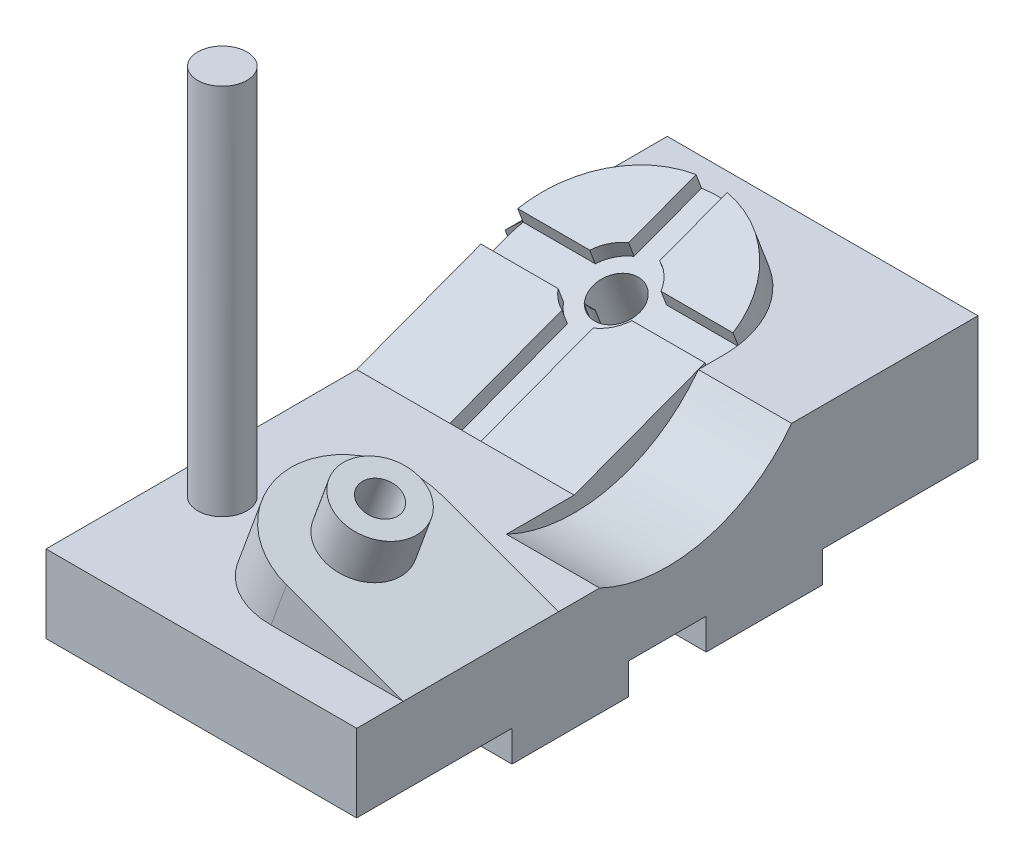
SolidWorks part; units mm, degrees
material "6061 Alloy"
ref_plane "Front Plane" through (0, 0, 0) normal (0, 0, 1) x (1, 0, 0)
ref_plane "Top Plane" through (0, 0, 0) normal (0, 1, 0) x (1, 0, 0)
ref_plane "Right Plane" through (0, 0, 0) normal (1, 0, 0) x (0, 0, -1)
sketch "Sketch1" plane through (0, 0, 0) normal (1, 0, 0) x (0, 0, -1)
  line L0 (173.8899, 19.6785) -> (173.8899, -20.3215)
  line L1 (123.8899, -20.3215) -> (123.8899, -30.3215)
  line L2 (123.8899, -30.3215) -> (86.3899, -30.3215)
  line L3 (86.3899, -30.3215) -> (86.3899, -20.3215)
  line L4 (86.3899, -20.3215) -> (61.3899, -20.3215)
  line L5 (61.3899, -20.3215) -> (61.3899, -30.3215)
  line L6 (61.3899, -30.3215) -> (23.8899, -30.3215)
  line L7 (23.8899, -30.3215) -> (23.8899, -20.3215)
  line L8 (23.8899, -20.3215) -> (-26.1101, -20.3215)
  line L9 (-26.1101, -20.3215) -> (-26.1101, 4.6785)
  line L10 (-26.1101, 4.6785) -> (52.0954, 4.6785)
  line L11 (113.8899, 19.6785) -> (173.8899, 19.6785)
  line L12 (173.8899, -20.3215) -> (123.8899, -20.3215)
  line L13 (73.8899, 4.6785) -> (73.8899, 49.6785) construction
  arc A1 (52.0954, 4.6785) -> (113.8899, 19.6785) centre (73.8899, 49.6785) ccw
  point P4 (-26.1101, -7.8215)
  point P17 (73.8899, 49.6785)
  dimension "D13" = 45
  dimension "D14" = 60
  dimension "D15" = 50
  dimension "D2" = 100
  dimension "D3" = 25
  dimension "D4" = 50
  dimension "D5" = 37.5
  dimension "D6" = 10
  dimension "D7" = 10
  dimension "D8" = 35
  dimension "D9" = 200
  dimension "D10" = 40
  dimension "D11" = 50
  dimension "D12" = 10
extrude "Boss-Extrude1" add sketch "Sketch1" along normal blind 30
sketch "Sketch2" plane through (0, 0, 0) normal (-1, 0, 0) x (0, 0, 1)
  line L0 (26.1101, 4.6785) -> (-73.8899, 4.6785)
  line L1 (-73.8899, 4.6785) -> (-113.8899, 19.6785)
  line L2 (-113.8899, 19.6785) -> (-173.8899, 19.6785)
  line L3 (-173.8899, 19.6785) -> (-173.8899, -20.3215)
  line L4 (-173.8899, -20.3215) -> (-123.8899, -20.3215)
  line L5 (-123.8899, -30.3215) -> (-123.8899, -20.3215) construction
  line L6 (-123.8899, -20.3215) -> (-173.8899, -20.3215) construction
  line L7 (-123.8899, -20.3215) -> (-123.8899, -30.3215)
  line L8 (-123.8899, -30.3215) -> (-86.3899, -30.3215)
  line L9 (-86.3899, -30.3215) -> (-86.3899, -20.3215)
  line L10 (-86.3899, -20.3215) -> (-86.3899, -30.3215) construction
  line L11 (-86.3899, -20.3215) -> (-61.3899, -20.3215)
  line L12 (-61.3899, -20.3215) -> (-61.3899, -30.3215)
  line L13 (-61.3899, -30.3215) -> (-23.8899, -30.3215)
  line L14 (-23.8899, -30.3215) -> (-23.8899, -20.3215)
  line L15 (-23.8899, -20.3215) -> (26.1101, -20.3215)
  line L16 (26.1101, -20.3215) -> (26.1101, 4.6785)
extrude "Boss-Extrude2" add sketch "Sketch2" along normal blind 70
sketch "Sketch3" plane through (0, -20.1909, -7.5716) normal (0, 0.9363, 0.3511) x (1, 0, 0)
  line L0 (-35, 70.828) -> (-35, 108.328) construction
  line L1 (-70, 70.828) -> (0, 70.828) construction
  line L2 (30, 169.7278) -> (30, 113.548) construction
  line L3 (-70, 113.548) -> (-70, 169.7278) construction
  line L4 (0, 70.828) -> (0, 113.548) construction
  line L5 (-70, 120.828) -> (-70, 115.828) construction
  line L6 (-70, 115.828) -> (-46.4564, 115.828)
  line L7 (0, -35.899) -> (0, 35.899) construction
  line L8 (0, 115.828) -> (0, 120.828)
  line L9 (-0.359, 125.828) -> (-23.5436, 125.828)
  line L10 (-70, 120.828) -> (-70, 115.828)
  line L11 (-35, 133.328) -> (-35, 155.828) construction
  line L12 (-70, 115.828) -> (-70, 70.828)
  line L13 (-70, -22.8049) -> (-70, 70.828) construction
  line L14 (-40, 155.469) -> (-40, 132.2845)
  line L15 (-70, 113.548) -> (0, 113.548) construction
  line L16 (-30, 70.828) -> (-30, 109.3716)
  line L17 (-70, 70.828) -> (-70, 113.548) construction
  line L18 (-70, 70.828) -> (0, 70.828)
  line L19 (0, 70.828) -> (0, 115.828)
  line L20 (-40, 109.3716) -> (-40, 70.828)
  line L22 (-30, 132.2845) -> (-30, 155.469)
  line L23 (-23.5436, 115.828) -> (0, 115.828)
  line L25 (-46.4564, 125.828) -> (-69.641, 125.828)
  circle A0 centre (-35, 120.828) radius 7.5
  circle A1 centre (-35, 120.828) radius 12.5
  arc A2 (-70, 120.828) -> (0, 120.828) centre (-35, 120.828) cw
  line M7 (0, 70.828) -> (0, 113.548)
  line M8 (0, 113.548) -> (-70, 113.548)
  line M9 (-70, 113.548) -> (-70, 70.828)
  line M10 (-70, 70.828) -> (0, 70.828)
  dimension "D1" = 15
  dimension "D2" = 25
  dimension "D3" = 0.359
  dimension "D4" = 30
  dimension "D5" = 2.28
  dimension "D6" = 7.28
sketch "Sketch5" plane through (30, 0, 0) normal (1, 0, 0) x (0, 0, -1)
  line L0 (157.8764, 19.6785) -> (201.3703, -5.4327) construction
  line L1 (173.8899, 19.6785) -> (113.8899, 19.6785) construction
  line L2 (157.8764, 19.6785) -> (203.9867, 19.6785) construction
  line L3 (157.8764, 19.6785) -> (187.5187, 36.7924) construction
  dimension "D1" = 30
  dimension "D2" = 150
extrude "Boss-Extrude4" add sketch "Sketch3" against normal blind 25 contours A1 L20 M8 M9 M10 | A1 L16 M10 M7 M8 | A2 L22 A1 L9 | A2 L25 A1 L14 | A2 L14 A1 L22 | A2 L10 L6 A1 L25 | A1 A0 M8 | A1 L20 L18 L16 | A0 M8 | A2 L9 A1 L23 L8 | A1 L19 L23 M8 | A1 L6 L12 M8 | A1 A0 M8 region at (-58.5473, 22.2312, -120.6972) region at (-57.928, 20.0752, -114.9478) region at (-47.1812, 22.2346, -120.7064) region at (-55.1321, 12.1084, -93.703) region at (-52.4515, 28.3623, -137.0468) region at (-35, 18.9252, -111.8813) region at (-35, 30.4922, -142.7265) region at (-35, 11.3225, -91.6073) region at (-35, 22.2424, -120.7272) region at (-17.5485, 28.3623, -137.0468) region at (-14.8679, 12.1084, -93.703) region at (-11.4527, 22.2312, -120.6972) region at (-12.072, 20.0752, -114.9478)
extrude "Cut-Extrude3" cut sketch "Sketch3<10>" against normal blind 5 contours A1 L6 L12 M8 | A2 L10 L6 A1 L25 | A1 A0 M8 | A1 A0 M8 | A2 L9 A1 L23 L8 | A1 L20 L18 L16 | A2 L14 A1 L22 region at (-58.5473, 22.2312, -120.6972) region at (-57.928, 20.0752, -114.9478) region at (-47.1812, 22.2346, -120.7064) region at (-35, 18.9252, -111.8813) region at (-35, 30.4922, -142.7265) region at (-35, 11.3225, -91.6073) region at (-11.4527, 22.2312, -120.6972)
sketch "Sketch3<10>" plane through (0, -20.1909, -7.5716) normal (0, 0.9363, 0.3511) x (1, 0, 0) same geometry as "Sketch3"
extrude "Cut-Extrude4" cut sketch "Sketch3<11>" against normal through all contours A0 M8 region at (-35, 22.2424, -120.7272)
sketch "Sketch3<11>" plane through (0, -20.1909, -7.5716) normal (0, 0.9363, 0.3511) x (1, 0, 0) same geometry as "Sketch3"
sketch "Sketch7" plane through (0, 0, 26.1101) normal (0, 0, 1) x (1, 0, 0)
  line L0 (30, 4.6785) -> (-8.7719, 4.6785) construction
  line L1 (-70, 4.6785) -> (0, 4.6785) construction
  line L2 (30, 4.6785) -> (-8.2602, 18.604) construction
  line L3 (30, 4.6785) -> (-7.5877, 18.3593)
  dimension "D1" = 20
sketch "Sketch8" plane through (0, 4.6785, 0) normal (0, 1, 0) x (1, 0, 0)
  line L0 (30, -26.1101) -> (30, -11.1101) construction
  line L1 (30, 52.0954) -> (30, -26.1101) construction
  line L2 (30, -11.1101) -> (30, 38.8899)
ref_plane "Plane1" through (5.013, 13.773, 0) normal (0.342, 0.9397, 0) x (0.9397, -0.342, 0)
sketch "Sketch10" plane through (5.013, 13.773, 0) normal (0.342, 0.9397, 0) x (0.9397, -0.342, 0)
  line L0 (26.5906, -11.1101) -> (26.5906, 38.8899)
  line L1 (26.5906, 38.8899) -> (-13.4094, 38.8899)
  line L2 (-13.4094, 38.8899) -> (-13.4094, 13.8899) construction
  line L3 (26.5906, -11.1101) -> (-13.4094, -11.1101)
  circle A0 centre (-13.4094, 13.8899) radius 6
  circle A1 centre (-13.4094, 13.8899) radius 12.5
  arc A2 (-13.4094, 38.8899) -> (-13.4094, -11.1101) centre (-13.4094, 13.8899) ccw
extrude "Boss-Extrude5" add sketch "Sketch10" against normal up to surface contours L1 A1 A2 L3 L0 region at (11.2061, 11.5189, 10.29) up to face at (-18.75, 4.6785, -43.4413)
extrude "Boss-Extrude6" add sketch "Sketch10<3>" along normal mid plane 30 separate body contours A1 A0 region at (-19.0016, 22.5136, -13.8899)
sketch "Sketch10<3>" plane through (5.013, 13.773, 0) normal (0.342, 0.9397, 0) x (0.9397, -0.342, 0) same geometry as "Sketch10"
extrude "Cut-Extrude5" cut sketch "Sketch10<4>" against normal through all contours A0 region at (-7.5877, 18.3593, -13.8899)
sketch "Sketch10<4>" plane through (5.013, 13.773, 0) normal (0.342, 0.9397, 0) x (0.9397, -0.342, 0) same geometry as "Sketch10"
sketch "Sketch11" plane through (0, 4.6785, 0) normal (0, 1, 0) x (1, 0, 0)
  circle A0 centre (-56.205, 16.8509) radius 7.9387
extrude "Boss-Extrude7" add sketch "Sketch11" along normal blind 120
